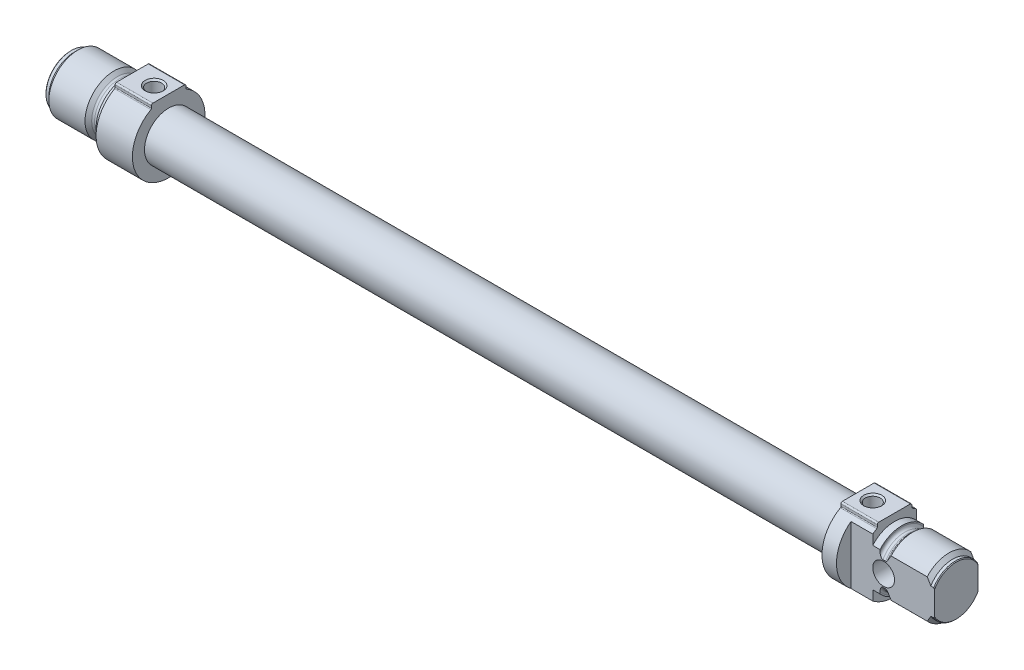
SolidWorks part; units mm, degrees
ref_plane "Ebene vorne" through (0, 0, 0) normal (0, 0, 1) x (1, 0, 0)
ref_plane "Ebene oben" through (0, 0, 0) normal (0, 1, 0) x (1, 0, 0)
ref_plane "Ebene rechts" through (0, 0, 0) normal (1, 0, 0) x (0, 0, -1)
sketch "Skizze1" plane through (0, 0, 0) normal (0, 0, 1) x (1, 0, 0)
  line L0 (0, 0) -> (0, 6.8)
  line L1 (0, 6.8) -> (0.2, 7)
  line L2 (0.2, 7) -> (1, 7)
  line L3 (1, 7) -> (2, 8)
  line L4 (2, 8) -> (11.95, 8)
  line L5 (11.95, 8) -> (12.8657, 7.0843)
  line L6 (13.4314, 6.85) -> (14.2, 6.85)
  line L7 (15, 7.65) -> (15, 8)
  line L8 (15, 8) -> (17, 8)
  line L9 (17, 8) -> (17, 0)
  line L10 (17, 0) -> (0, 0)
  line L11 (17, 0) -> (0, 0) construction
  arc A0 (12.8657, 7.0843) -> (13.4314, 6.85) centre (13.4314, 7.65) ccw
  arc A1 (14.2, 6.85) -> (15, 7.65) centre (14.2, 7.65) ccw
revolve "Rotation1" add sketch "Skizze1" angle 360 about L11 reverse direction yes
cosmetic thread "Gewindedarstellung1" parameters "D1"=10.87, "D2"=14.16
ref_plane "Ebene1" through (21.1, 0, 0) normal (1, 0, 0) x (0, 0, -1)
ref_plane "Ebene2" through (9, 0, 0) normal (1, 0, 0) x (0, 0, -1)
ref_plane "Ebene3" through (0, -11, 0) normal (0, 1, 0) x (1, 0, 0)
ref_plane "Ebene4" through (0, 11, 0) normal (0, 1, 0) x (1, 0, 0)
ref_plane "Ebene5" through (0, 0, 0) normal (0, 1, 0) x (1, 0, 0)
ref_plane "Ebene6" through (0, 0, 0) normal (0, 1, 0) x (1, 0, 0)
ref_plane "Ebene7" through (17, 0, 0) normal (1, 0, 0) x (0, 0, -1)
ref_plane "Ebene8" through (17, 0, 0) normal (1, 0, 0) x (0, 0, -1)
ref_plane "Ebene9" through (27, 0, 0) normal (1, 0, 0) x (0, 0, -1)
ref_plane "Ebene10" through (17, 0, 0) normal (1, 0, 0) x (0, 0, -1)
ref_plane "Ebene11" through (17, 0, 0) normal (1, 0, 0) x (0, 0, -1)
sketch "Skizze2" plane through (17, 0, 0) normal (1, 0, 0) x (0, 0, -1)
  line L0 (4.75, 8.9771) -> (4.75, 9.6)
  line L1 (4.35, 10) -> (-4.35, 10)
  line L2 (-4.75, 9.6) -> (-4.75, 8.9771)
  arc A0 (-4.9029, 8.7156) -> (4.9029, 8.7156) centre (0, 0) ccw
  arc A1 (4.9029, 8.7156) -> (4.75, 8.9771) centre (5.05, 8.9771) cw
  arc A2 (4.75, 9.6) -> (4.35, 10) centre (4.35, 9.6) ccw
  arc A3 (-4.35, 10) -> (-4.75, 9.6) centre (-4.35, 9.6) ccw
  arc A4 (-4.75, 8.9771) -> (-4.9029, 8.7156) centre (-5.05, 8.9771) cw
extrude "Aufsatz-Linear austragen1" add sketch "Skizze2" along normal blind 10
ref_plane "Ebene12" through (23, 0, 0) normal (1, 0, 0) x (0, 0, -1)
ref_plane "Ebene13" through (0, 0, 0) normal (0, 0, 1) x (1, 0, 0)
ref_plane "Ebene14" through (0, 0, -5.7) normal (0, 0, 1) x (1, 0, 0)
ref_plane "Ebene15" through (0, 0, 0) normal (0, 1, 0) x (1, 0, 0)
ref_plane "Ebene16" through (0, 7.5, 0) normal (0, 1, 0) x (1, 0, 0)
ref_plane "Ebene17" through (0, 0, -6.6) normal (0, 0, 1) x (1, 0, 0)
ref_plane "Ebene18" through (0, 0, 0) normal (0, 1, 0) x (1, 0, 0)
ref_plane "Ebene19" through (0, 7.5, 0) normal (0, 1, 0) x (1, 0, 0)
ref_plane "Ebene20" through (0, 8.4025, -1.4816) normal (0, 0.9848, -0.1736) x (1, 0, 0)
ref_plane "Ebene21" through (0, 6.9253, -1.2211) normal (0, 0.9848, -0.1736) x (1, 0, 0)
sketch "Skizze3" plane through (0, 0, 0) normal (0, 0, 1) x (1, 0, 0)
  line L0 (27, 0) -> (27, 6.65)
  line L1 (27, 6.65) -> (217, 6.65)
  line L2 (217, 6.65) -> (217, 0)
  line L3 (217, 0) -> (27, 0)
  line L4 (217, 0) -> (27, 0) construction
revolve "Rotation2" add sketch "Skizze3" angle 360 about L4 reverse direction yes
ref_plane "Ebene22" through (217, 0, 0) normal (1, 0, 0) x (0, 0, -1)
sketch "Skizze4" plane through (217, 0, 0) normal (1, 0, 0) x (0, 0, -1)
  line L0 (4.75, 8.9771) -> (4.75, 9.6)
  line L1 (4.35, 10) -> (-4.35, 10)
  line L2 (-4.75, 9.6) -> (-4.75, 8.9771)
  arc A0 (-4.9029, 8.7156) -> (4.9029, 8.7156) centre (0, 0) ccw
  arc A1 (4.9029, 8.7156) -> (4.75, 8.9771) centre (5.05, 8.9771) cw
  arc A2 (4.75, 9.6) -> (4.35, 10) centre (4.35, 9.6) ccw
  arc A3 (-4.35, 10) -> (-4.75, 9.6) centre (-4.35, 9.6) ccw
  arc A4 (-4.75, 8.9771) -> (-4.9029, 8.7156) centre (-5.05, 8.9771) cw
extrude "Aufsatz-Linear austragen2" add sketch "Skizze4" along normal blind 10
ref_plane "Ebene23" through (218.85, 0, 0) normal (1, 0, 0) x (0, 0, -1)
ref_plane "Ebene24" through (221, 0, 0) normal (1, 0, 0) x (0, 0, -1)
ref_plane "Ebene25" through (0, 0, 6.6) normal (0, 0, 1) x (1, 0, 0)
ref_plane "Ebene26" through (0, 0, 0) normal (0, 1, 0) x (1, 0, 0)
ref_plane "Ebene27" through (0, 7.5, 0) normal (0, 1, 0) x (1, 0, 0)
ref_plane "Ebene28" through (0, 8.4025, 1.4816) normal (0, 0.9848, 0.1736) x (1, 0, 0)
ref_plane "Ebene29" through (0, 6.9253, 1.2211) normal (0, 0.9848, 0.1736) x (1, 0, 0)
ref_plane "Ebene30" through (265, 0, 0) normal (1, 0, 0) x (0, 0, -1)
sketch "Skizze5" plane through (0, 0, 0) normal (0, 0, 1) x (1, 0, 0)
  line L0 (227, 0) -> (227, 8)
  line L1 (227, 8) -> (229, 8)
  line L2 (229, 8) -> (229, 7.65)
  line L3 (229.8, 6.85) -> (230.5686, 6.85)
  line L4 (231.1343, 7.0843) -> (232.05, 8)
  line L5 (232.05, 8) -> (242, 8)
  line L6 (242, 8) -> (243, 7)
  line L7 (243, 7) -> (243.8, 7)
  line L8 (243.8, 7) -> (244, 6.8)
  line L9 (244, 6.8) -> (244, 0)
  line L10 (244, 0) -> (227, 0)
  line L11 (244, 0) -> (227, 0) construction
  arc A0 (229, 7.65) -> (229.8, 6.85) centre (229.8, 7.65) ccw
  arc A1 (230.5686, 6.85) -> (231.1343, 7.0843) centre (230.5686, 7.65) ccw
revolve "Rotation3" add sketch "Skizze5" angle 360 about L11 reverse direction yes
cosmetic thread "Gewindedarstellung2" parameters "D1"=9.87, "D2"=14.16
ref_plane "Ebene31" through (255, 0, 0) normal (1, 0, 0) x (0, 0, -1)
ref_plane "Ebene32" through (265, 0, 0) normal (1, 0, 0) x (0, 0, -1)
ref_plane "Ebene33" through (265, 0, 0) normal (1, 0, 0) x (0, 0, -1)
sketch "Skizze6" plane through (0, 0, 0) normal (0, 1, 0) x (1, 0, 0)
  line L0 (221, 18) -> (221, 6)
  line L1 (221, 6) -> (244, 6)
  line L2 (244, 6) -> (244, -6)
  line L3 (244, -6) -> (221, -6)
  line L4 (221, -6) -> (221, -18)
  line L5 (221, -18) -> (256, -18)
  line L6 (256, -18) -> (256, 18)
  line L7 (256, 18) -> (221, 18)
extrude "Schnitt-Linear austragen1" cut sketch "Skizze6" along normal blind 10 and the other way blind 10
ref_plane "Ebene34" through (230, 0, 0) normal (1, 0, 0) x (0, 0, -1)
hole_wizard "Bohrung1" positions "Skizze8" profile "Skizze7" legacy
sketch "Skizze8" plane through (0, 0, -6) normal (0, 0, -1) x (-1, 0, 0)
  point P0 (-230, 0)
sketch "Skizze7" plane through (230, 0, -6) normal (1, 0, 0) x (0, 1, 0)
  line L0 (0, 0) -> (0, 12)
  line L1 (0, 12) -> (3, 12)
  line L2 (3, 12) -> (3, 0)
  line L3 (3, 0) -> (0, 0)
  line L4 (0, 110) -> (0, -10) construction
  dimension "Durchmesser" = 6
  dimension "Tiefe" = 12
hole_wizard "Bohrung2" positions "Skizze10" profile "Skizze9" legacy
sketch "Skizze10" plane through (0, 10, 0) normal (0, 1, 0) x (1, 0, 0)
  point P0 (23, 0)
sketch "Skizze9" plane through (23, 10, 0) normal (1, 0, 0) x (0, 0, 1)
  line L0 (0, 0) -> (0, 10)
  line L1 (0, 10) -> (2.067, 10)
  line L2 (2.067, 10) -> (2.067, 0.433)
  line L3 (2.067, 0.433) -> (2.5, 0)
  line L4 (2.5, 0) -> (0, 0)
  line L5 (0, -6.4453) -> (0, 115.525) construction
  line L6 (-2.067, 0.433) -> (-2.5, 0) construction
  dimension "Durchmesser" = 4.134
  dimension "Tiefe" = 10
  dimension "Senkwinkel1" = 90
  dimension "Senkdurchmesser3" = 5
cosmetic thread "Gewindedarstellung3" parameters "D1"=7, "D2"=5
hole_wizard "Bohrung3" positions "Skizze12" profile "Skizze11" legacy
sketch "Skizze12" plane through (0, 10, 0) normal (0, 1, 0) x (1, 0, 0)
  point P0 (221, 0)
sketch "Skizze11" plane through (221, 10, 0) normal (1, 0, 0) x (0, 0, 1)
  line L0 (0, 0) -> (0, 12.1934)
  line L1 (0, 12.1934) -> (2.067, 11)
  line L2 (2.067, 11) -> (2.067, 0.433)
  line L3 (2.067, 0.433) -> (2.5, 0)
  line L4 (2.5, 0) -> (0, 0)
  line L5 (0, -14.3089) -> (0, 102.4216) construction
  line L6 (0, 12.1934) -> (-2.067, 11) construction
  line L7 (-2.067, 0.433) -> (-2.5, 0) construction
  dimension "Durchmesser" = 4.134
  dimension "Tiefe" = 11
  dimension "Senkdurchmesser1" = 5
  dimension "Senkwinkel1" = 90
  dimension "Spitzenwinkel" = 120
cosmetic thread "Gewindedarstellung4" parameters "D1"=6, "D2"=5
sketch "Skizze13" plane through (0, 0, 0) normal (0, 0, 1) x (1, 0, 0)
  line L0 (-5, 0) -> (-5, 3)
  line L1 (-5, 3) -> (37.3, 3)
  line L2 (37.3, 3) -> (37.3, 6)
  line L3 (37.3, 6) -> (200.3, 6)
  line L4 (200.3, 6) -> (200.3, 0)
  line L5 (200.3, 0) -> (-5, 0)
  line L6 (200.3, 0) -> (-5, 0) construction
revolve "Schnitt-Rotation1" cut sketch "Skizze13" angle 360 about L6 reverse direction yes
ref_plane "Ebene35" through (-5, 0, 0) normal (1, 0, 0) x (0, 0, -1)
ref_plane "Ebene36" through (0, 10, 0) normal (0, 1, 0) x (1, 0, 0)
ref_plane "Ebene37" through (8, 0, 0) normal (1, 0, 0) x (0, 0, -1)
ref_plane "Ebene38" through (0, 0, 0) normal (1, 0, 0) x (0, 0, -1)
ref_plane "Ebene39" through (17, 0, 0) normal (1, 0, 0) x (0, 0, -1)
ref_plane "Ebene40" through (227, 0, 0) normal (1, 0, 0) x (0, 0, -1)
ref_plane "Ebene41" through (17, 0, 0) normal (1, 0, 0) x (0, 0, -1)
ref_plane "Ebene42" through (0, 10, 0) normal (0, 1, 0) x (1, 0, 0)
ref_plane "Ebene43" through (36.5, 0, 0) normal (1, 0, 0) x (0, 0, -1)
ref_plane "Ebene44" through (207.5, 0, 0) normal (1, 0, 0) x (0, 0, -1)
ref_plane "Ebene45" through (0, 0, 0) normal (0, 0, 1) x (1, 0, 0)
ref_plane "Ebene46" through (17, 0, 0) normal (1, 0, 0) x (0, 0, -1)
ref_plane "Ebene47" through (0, 10, 0) normal (0, 1, 0) x (1, 0, 0)
ref_plane "FDT_FRONT XY" through (17, 0, 0) normal (1, 0, 0) x (0, 0, -1)
ref_plane "FDT_FRONT XZ" through (0, 0, 0) normal (0, -1, 0) x (-1, 0, 0)
ref_plane "FDT_FRONT YZ" through (0, 0, 0) normal (0, 0, -1) x (-1, 0, 0)
ref_axis "FDT_FRONT X" through (17, 0, 80.9) along (0, 0, -1)
ref_axis "FDT_FRONT Y" through (17, -50, 0) along (0, 1, 0)
ref_axis "FDT_FRONT Z" through (80.9, 0, 0) along (-1, 0, 0)
sketch3d "FDT_FRONT"
  point P0 (17, 0, 0)
ref_plane "FDT_QSFRONT XY" through (0, 10, 0) normal (0, 1, 0) x (1, 0, 0)
ref_plane "FDT_QSFRONT XZ" through (23, 0, 0) normal (-1, 0, 0) x (0, 0, 1)
ref_plane "FDT_QSFRONT YZ" through (0, 0, 0) normal (0, 0, 1) x (1, 0, 0)
ref_axis "FDT_QSFRONT X" through (23, 10, -50) along (0, 0, 1)
ref_axis "FDT_QSFRONT Y" through (-80.9, 10, 0) along (1, 0, 0)
ref_axis "FDT_QSFRONT Z" through (23, 50, 0) along (0, -1, 0)
sketch3d "FDT_QSFRONT"
  point P0 (23, 10, 0)
ref_plane "FDT_QSREAR XY" through (0, 10, 0) normal (0, 1, 0) x (1, 0, 0)
ref_plane "FDT_QSREAR XZ" through (221, 0, 0) normal (-1, 0, 0) x (0, 0, 1)
ref_plane "FDT_QSREAR YZ" through (0, 0, 0) normal (0, 0, 1) x (1, 0, 0)
ref_axis "FDT_QSREAR X" through (221, 10, -50) along (0, 0, 1)
ref_axis "FDT_QSREAR Y" through (-80.9, 10, 0) along (1, 0, 0)
ref_axis "FDT_QSREAR Z" through (221, 50, 0) along (0, -1, 0)
sketch3d "FDT_QSREAR"
  point P0 (221, 10, 0)
ref_plane "FDT_REAR XY" through (227, 0, 0) normal (-1, 0, 0) x (0, 0, 1)
ref_plane "FDT_REAR XZ" through (0, 0, 0) normal (0, 1, 0) x (1, 0, 0)
ref_plane "FDT_REAR YZ" through (0, 0, 0) normal (0, 0, -1) x (-1, 0, 0)
ref_axis "FDT_REAR X" through (227, 0, 80.9) along (0, 0, -1)
ref_axis "FDT_REAR Y" through (227, 50, 0) along (0, -1, 0)
ref_axis "FDT_REAR Z" through (-80.9, 0, 0) along (1, 0, 0)
sketch3d "FDT_REAR"
  point P0 (227, 0, 0)
ref_plane "FDT_SMBR1 XY" through (36.5, 0, 0) normal (-1, 0, 0) x (0, 0, 1)
ref_plane "FDT_SMBR1 XZ" through (0, 0, 0) normal (0, -1, 0) x (-1, 0, 0)
ref_plane "FDT_SMBR1 YZ" through (0, 0, 0) normal (0, 0, 1) x (1, 0, 0)
ref_axis "FDT_SMBR1 X" through (36.5, 0, -80.9) along (0, 0, 1)
ref_axis "FDT_SMBR1 Y" through (36.5, -50, 0) along (0, 1, 0)
ref_axis "FDT_SMBR1 Z" through (-80.9, 0, 0) along (1, 0, 0)
sketch3d "FDT_SMBR1"
  point P0 (36.5, 0, 0)
ref_plane "FDT_SMBR2 XY" through (207.5, 0, 0) normal (-1, 0, 0) x (0, 0, 1)
ref_plane "FDT_SMBR2 XZ" through (0, 0, 0) normal (0, -1, 0) x (-1, 0, 0)
ref_plane "FDT_SMBR2 YZ" through (0, 0, 0) normal (0, 0, 1) x (1, 0, 0)
ref_axis "FDT_SMBR2 X" through (207.5, 0, -80.9) along (0, 0, 1)
ref_axis "FDT_SMBR2 Y" through (207.5, -50, 0) along (0, 1, 0)
ref_axis "FDT_SMBR2 Z" through (-80.9, 0, 0) along (1, 0, 0)
sketch3d "FDT_SMBR2"
  point P0 (207.5, 0, 0)
ref_plane "FDT_SWIVELAXIS XY" through (0, 0, 0) normal (0, 0, 1) x (1, 0, 0)
ref_plane "FDT_SWIVELAXIS XZ" through (0, 0, 0) normal (0, -1, 0) x (-1, 0, 0)
ref_plane "FDT_SWIVELAXIS YZ" through (230, 0, 0) normal (1, 0, 0) x (0, 0, -1)
ref_axis "FDT_SWIVELAXIS X" through (-80.9, 0, 0) along (1, 0, 0)
ref_axis "FDT_SWIVELAXIS Y" through (230, -50, 0) along (0, 1, 0)
ref_axis "FDT_SWIVELAXIS Z" through (230, 0, 80.9) along (0, 0, -1)
sketch3d "FDT_SWIVELAXIS"
  point P0 (230, 0, 0)
ref_plane "NUT XY" through (8, 0, 0) normal (1, 0, 0) x (0, 0, -1)
ref_plane "NUT XZ" through (0, 0, 0) normal (0, -1, 0) x (-1, 0, 0)
ref_plane "NUT YZ" through (0, 0, 0) normal (0, 0, -1) x (-1, 0, 0)
ref_axis "NUT X" through (8, 0, 80.9) along (0, 0, -1)
ref_axis "NUT Y" through (8, -50, 0) along (0, 1, 0)
ref_axis "NUT Z" through (80.9, 0, 0) along (-1, 0, 0)
sketch3d "NUT"
  point P0 (8, 0, 0)
ref_plane "ZR XY" through (0, 0, 0) normal (1, 0, 0) x (0, 0, -1)
ref_plane "ZR XZ" through (0, 0, 0) normal (0, -1, 0) x (-1, 0, 0)
ref_plane "ZR YZ" through (0, 0, 0) normal (0, 0, -1) x (-1, 0, 0)
ref_axis "ZR X" through (0, 0, 80.9) along (0, 0, -1)
ref_axis "ZR Y" through (0, -50, 0) along (0, 1, 0)
ref_axis "ZR Z" through (80.9, 0, 0) along (-1, 0, 0)
sketch3d "ZR"
  point P0 (0, 0, 0)
ref_plane "ZYL XY" through (17, 0, 0) normal (1, 0, 0) x (0, 0, -1)
ref_plane "ZYL XZ" through (0, 0, 0) normal (0, -1, 0) x (-1, 0, 0)
ref_plane "ZYL YZ" through (0, 0, 0) normal (0, 0, -1) x (-1, 0, 0)
ref_axis "ZYL X" through (17, 0, 80.9) along (0, 0, -1)
ref_axis "ZYL Y" through (17, -50, 0) along (0, 1, 0)
ref_axis "ZYL Z" through (80.9, 0, 0) along (-1, 0, 0)
sketch3d "ZYL"
  point P0 (17, 0, 0)
